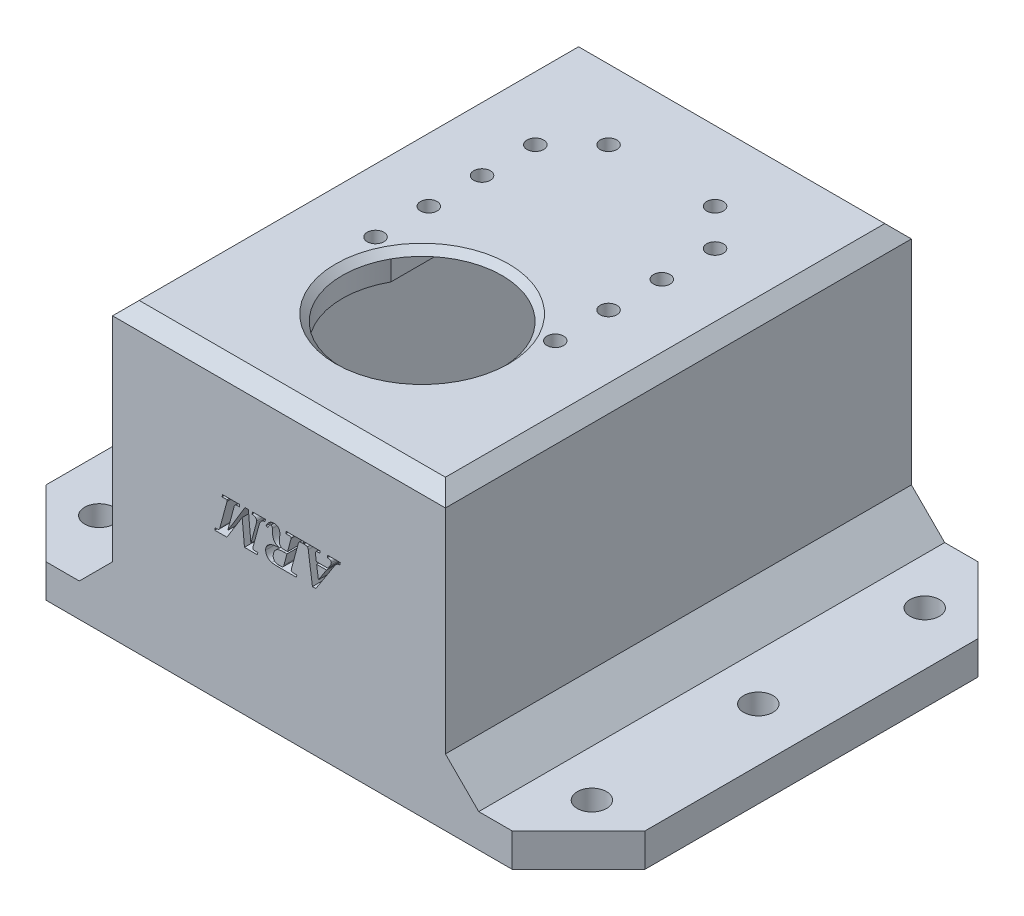
SolidWorks part; units mm, degrees
ref_plane "Front Plane" through (0, 0, 0) normal (0, 0, 1) x (1, 0, 0)
ref_plane "Top Plane" through (0, 0, 0) normal (0, 1, 0) x (1, 0, 0)
ref_plane "Right Plane" through (0, 0, 0) normal (1, 0, 0) x (0, 0, -1)
sketch "Sketch1" plane through (0, 0, 0) normal (0, 1, 0) x (1, 0, 0)
  line L1 (-25, 35) -> (25, 35)
  line L2 (-25, 35) -> (-25, -35)
  line L3 (-25, -35) -> (25, -35)
  line L4 (25, 35) -> (25, -35)
  line L5 (-25, 35) -> (25, -35) construction
  line L6 (-25, -35) -> (25, 35) construction
  point P0 (0, 0)
  dimension "D1" = 50
  dimension "D2" = 70
extrude "Boss-Extrude1" add sketch "Sketch1" along normal blind 4
sketch "Sketch3" plane through (0, 0, 0) normal (0, -1, 0) x (-1, 0, 0)
  line L0 (0, -35) -> (0, -13.5) construction
  line L1 (25, -35) -> (-25, -35) construction
  circle A0 centre (0, -13.5) radius 12
  dimension "D2" = 24
  dimension "D1" = 21.5
extrude "Cut-Extrude1" cut sketch "Sketch3" against normal through all
sketch "Sketch4" plane through (0, 0, 0) normal (0, -1, 0) x (-1, 0, 0)
  line L0 (0, -13.5) -> (0, 18.5) construction
  line L1 (0, 18.5) -> (-10.5, 18.5) construction
  line L2 (-10.5, 18.5) -> (10.5, 18.5)
  line L3 (10.5, 18.5) -> (10.5, -7.6905)
  line L4 (-10.5, 18.5) -> (-10.5, -7.6905)
  circle A0 centre (0, -13.5) radius 12 construction
  arc A1 (10.5, -7.6905) -> (-10.5, -7.6905) centre (0, -13.5) ccw
  dimension "D1" = 32
  dimension "D2" = 10.5
extrude "Cut-Extrude2" cut sketch "Sketch4" against normal blind 3
sketch "Sketch5" plane through (0, 0, 0) normal (0, -1, 0) x (-1, 0, 0)
  line L0 (0, 0) -> (-8, 0) construction
  line L1 (0, 0) -> (8, 0) construction
  line L2 (0, 0) -> (-13.5, 0) construction
  line L3 (0, 0) -> (13.5, 0) construction
  line L4 (0, -13.5) -> (0, -7) construction
  line L5 (0, -7) -> (0, 1) construction
  line L6 (0, 1) -> (0, 9) construction
  line L7 (0, 9) -> (0, 17) construction
  line L8 (0, 17) -> (0, 22.5) construction
  circle A0 centre (13.5, -7) radius 1.25
  circle A1 centre (13.5, 1) radius 1.25
  circle A2 centre (13.5, 9) radius 1.25
  circle A3 centre (13.5, 17) radius 1.25
  circle A4 centre (8, 22.5) radius 1.25
  circle A5 centre (-8, 22.5) radius 1.25
  circle A6 centre (-13.5, 17) radius 1.25
  circle A7 centre (-13.5, 9) radius 1.25
  circle A8 centre (-13.5, 1) radius 1.25
  circle A9 centre (-13.5, -7) radius 1.25
  dimension "D7" = 2.5
  dimension "D1" = 6.5
  dimension "D2" = 8
  dimension "D3" = 8
  dimension "D4" = 8
  dimension "D5" = 16
  dimension "D6" = 27
extrude "Cut-Extrude3" cut sketch "Sketch5" against normal through all
sketch "Sketch6" plane through (0, 0, 0) normal (0, -1, 0) x (-1, 0, 0)
  line L2 (25, -35) -> (-25, -35)
  line L3 (25, -35) -> (25, 35)
  line L4 (25, 35) -> (-25, 35)
  line L5 (-25, -35) -> (-25, 35)
  line L6 (25, -35) -> (-25, 35) construction
  line L7 (25, 35) -> (-25, -35) construction
  line L8 (22, -32) -> (-22, -32)
  line L9 (22, -32) -> (22, 32)
  line L10 (22, 32) -> (-22, 32)
  line L11 (-22, -32) -> (-22, 32)
  line L12 (22, -32) -> (-22, 32) construction
  line L13 (22, 32) -> (-22, -32) construction
  point P0 (0, 0)
  point P6 (0, 0)
  dimension "D1" = 44
  dimension "D2" = 64
extrude "Boss-Extrude2" add sketch "Sketch6" along normal blind 40
chamfer "Chamfer1" distance 2 angle 45 8 edges at (22, 0, 0) (0, 0, -32) (-22, 0, 0) (0, 0, 32) (0, 4, 35) (-25, 4, 0) (25, 4, 0) (0, 4, -35)
chamfer "Chamfer2" distance 1 angle 45 1 edges at (0, 4, 1.5)
sketch "Sketch7" plane through (0, -40, 0) normal (0, -1, 0) x (-1, 0, 0)
  line L0 (-25, -35) -> (-45, -35)
  line L1 (-45, -35) -> (-45, 35)
  line L2 (-45, 35) -> (-25, 35)
  line L3 (-25, 35) -> (-25, -35)
  line L4 (25, -35) -> (45, -35)
  line L5 (45, -35) -> (45, 35)
  line L6 (45, 35) -> (25, 35)
  line L7 (25, 35) -> (25, -35)
  line L8 (45, 0) -> (37, 0) construction
  line L9 (37, 0) -> (37, -25) construction
  line L10 (37, 0) -> (37, 25) construction
  line L11 (-45, 0) -> (-37, 0) construction
  circle A0 centre (37, -25) radius 2.2
  circle A1 centre (-37, -25) radius 2.2
  circle A2 centre (-37, 0) radius 2.2
  circle A3 centre (-37, 25) radius 2.2
  circle A4 centre (37, 0) radius 2.2
  circle A5 centre (37, 25) radius 2.2
  dimension "D3" = 2
  dimension "D1" = 8
  dimension "D2" = 8
  dimension "D4" = 3
extrude "Boss-Extrude3" add sketch "Sketch7" against normal blind 5
chamfer "Chamfer3" distance 10 angle 45 4 edges at (45, -37.5, -35) (45, -37.5, 35) (-45, -37.5, -35) (-45, -37.5, 35)
chamfer "Chamfer4" distance 5 angle 45 2 edges
sketch "Sketch8" plane through (0, 0, -35) normal (0, 0, -1) x (-1, 0, 0)
  line L0 (0, -40) -> (10, -40)
  line L1 (35, -40) -> (-35, -40) construction
  line L2 (10, -40) -> (10, -35)
  line L3 (10, -35) -> (-10, -35)
  line L4 (-10, -35) -> (-10, -40)
  line L5 (-10, -40) -> (0, -40)
  dimension "D1" = 20
  dimension "D2" = 5
extrude "Cut-Extrude4" cut sketch "Sketch8" against normal blind 5
fillet "Fillet1" radius 2 4 edges at (10, -35, -33.5) (10, -40, -33.5) (-10, -35, -33.5) (-10, -40, -33.5)
sketch "Sketch9" plane through (0, 0, 35) normal (0, 0, 1) x (1, 0, 0)
  line L0 (0, 2) -> (0, -13) construction
  line L1 (25, 2) -> (-25, 2) construction
  line L3 (-25, 2) -> (-25, -30) construction
  line L4 (-25, -13) -> (25, -13) construction
  line L5 (25, 2) -> (25, -30) construction
  text T0 "ARM" font "Century Schoolbook" height in points 20
  dimension "D1" = 15
extrude "Cut-Extrude5" cut sketch "Sketch9" against normal blind 3
